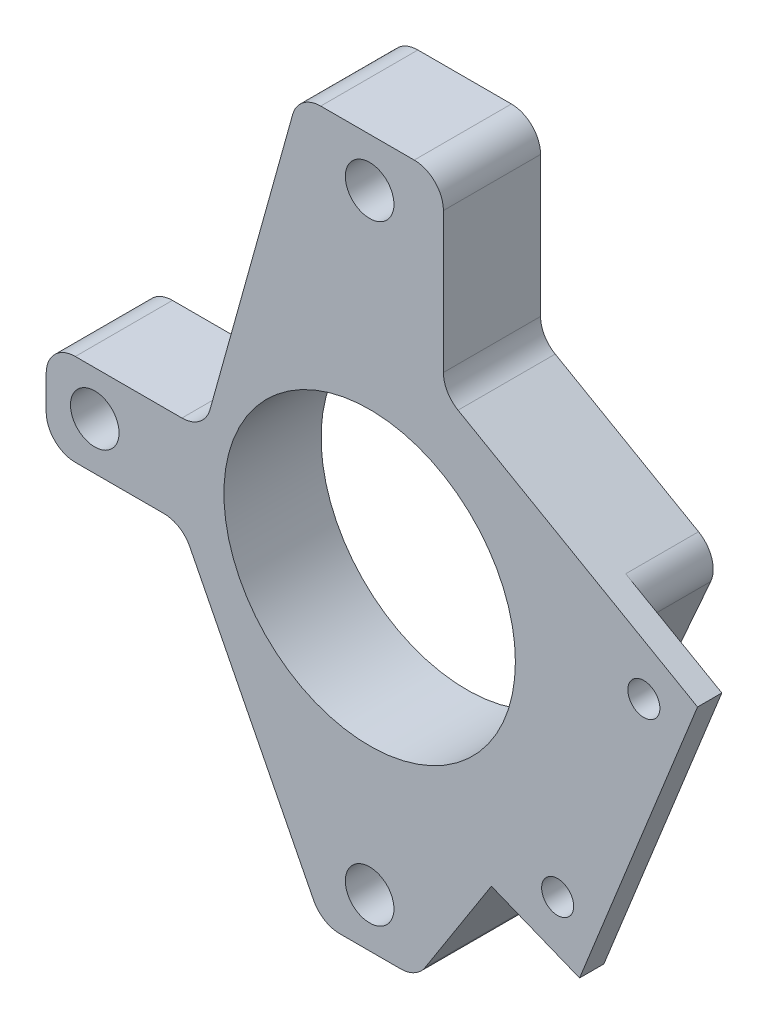
SolidWorks part; units mm, degrees
ref_plane "Front Plane" through (0, 0, 0) normal (0, 0, 1) x (1, 0, 0)
ref_plane "Top Plane" through (0, 0, 0) normal (0, 1, 0) x (1, 0, 0)
ref_plane "Right Plane" through (0, 0, 0) normal (1, 0, 0) x (0, 0, -1)
sketch "Sketch1" plane through (0, 0, 0) normal (0, 0, 1) x (1, 0, 0)
  line L0 (-18.5763, 100.3652) -> (19.2813, 100.3652)
  line L1 (19.2813, 100.3652) -> (19.2813, 51.6625)
  line L2 (19.2813, 51.6625) -> (85.7172, 13.5763)
  line L3 (85.7172, 13.5763) -> (54.8801, -63.2031)
  line L7 (12.2455, -84.5312) -> (-12.5308, -84.5312)
  line L9 (-12.5308, -84.5312) -> (-49.1135, -12.3821)
  line L10 (-49.1135, -12.3821) -> (-84.5631, -12.3821)
  line L11 (-84.5631, -12.3821) -> (-84.5631, 11.5981)
  line L12 (-84.5631, 11.5981) -> (-43.2846, 11.5981)
  line L13 (-43.2846, 11.5981) -> (-18.5763, 100.3652)
  line L14 (54.8801, -63.2031) -> (31.8266, -53.9441)
  line L15 (31.8266, -53.9441) -> (12.2455, -84.5312)
  circle A0 centre (0, 0) radius 38.1
  circle A3 centre (0, 87.6652) radius 6.35
  circle A4 centre (0, -71.8312) radius 6.35
  circle A5 centre (-71.8631, 0) radius 6.35
  point P3 (0, -71.8312)
  point P4 (0, 0)
  point P5 (0, 0)
  dimension "D1" = 76.2
  dimension "D2" = 12.7
  dimension "D3" = 12.7
  dimension "D4" = 12.7
extrude "Boss-Extrude1" add sketch "Sketch1" along normal blind 25.4
sketch "Sketch2" plane through (0, 0, 0) normal (0, 0, 1) x (1, 0, 0)
  line L2 (85.7172, 13.5763) -> (54.8801, -63.2031)
  line L5 (85.7172, 13.5763) -> (66.5382, 24.5712)
  line L6 (85.7172, 13.5763) -> (19.2813, 51.6625) construction
  line L7 (66.5382, 24.5712) -> (31.8266, -53.9441)
  line L8 (54.8801, -63.2031) -> (31.8266, -53.9441)
extrude "Cut-Extrude1" cut sketch "Sketch2" along normal blind 19.05 contours L8 L7 L5 L2
sketch "Sketch3" plane through (0, 0, 25.4) normal (0, 0, 1) x (1, 0, 0)
  circle A0 centre (71.6792, 8.3618) radius 4.191
  circle A1 centre (49.1489, -47.7348) radius 4.191
  dimension "D1" = 8.382
  dimension "D2" = 8.382
  dimension "D3" = 60.452
extrude "Cut-Extrude2" cut sketch "Sketch3" against normal through all
fillet "Fillet1" radius 7.62 10 edges at (-18.5763, 100.3652, 12.7) (19.2813, 100.3652, 12.7) (19.2813, 51.6625, 12.7) (66.5382, 24.5712, 9.525) (-49.1135, -12.3821, 12.7) (-84.5631, -12.3821, 12.7) (-84.5631, 11.5981, 12.7) (-43.2846, 11.5981, 12.7) (12.2455, -84.5312, 12.7) (-12.5308, -84.5312, 12.7)
